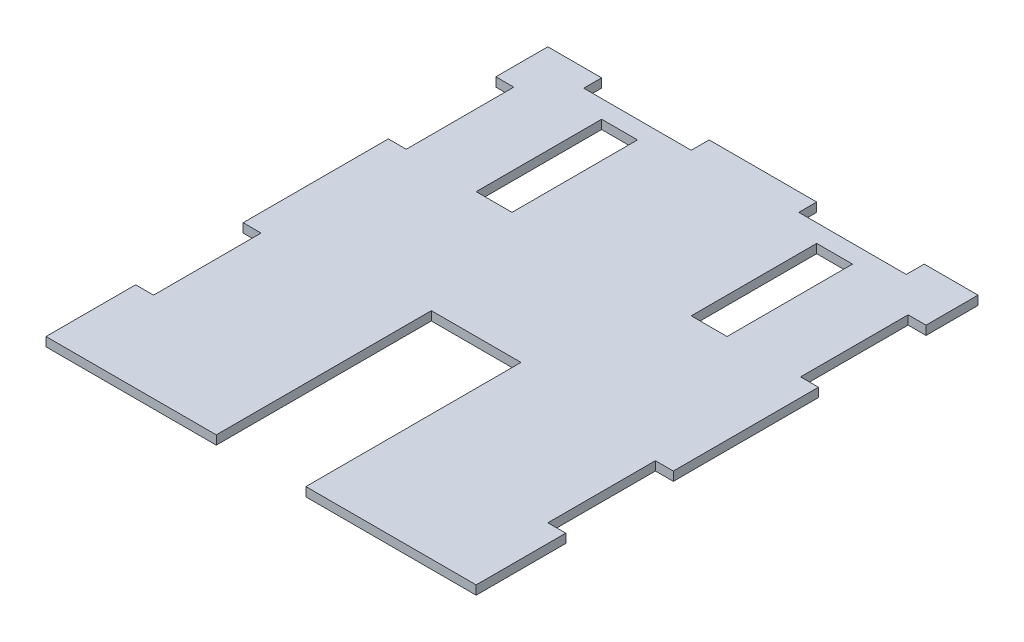
SolidWorks part; units mm, degrees
ref_plane "Front Plane" through (0, 0, 0) normal (0, 0, 1) x (1, 0, 0)
ref_plane "Top Plane" through (0, 0, 0) normal (0, 1, 0) x (1, 0, 0)
ref_plane "Right Plane" through (0, 0, 0) normal (1, 0, 0) x (0, 0, -1)
sketch "Sketch1" plane through (0, 0, 0) normal (0, 1, 0) x (1, 0, 0)
  line L1 (-152.4, -177.8) -> (152.4, -177.8)
  line L2 (-152.4, -177.8) -> (-152.4, 177.8)
  line L3 (-152.4, 177.8) -> (152.4, 177.8)
  line L4 (152.4, -177.8) -> (152.4, 177.8)
  line L5 (-152.4, -177.8) -> (152.4, 177.8) construction
  line L6 (-152.4, 177.8) -> (152.4, -177.8) construction
  point P0 (0, 0)
  dimension "D1" = 355.6
  dimension "D2" = 304.8
extrude "Boss-Extrude1" add sketch "Sketch1" along normal blind 6.35
sketch "Sketch2" plane through (0, 6.35, 0) normal (0, 1, 0) x (1, 0, 0)
  line L0 (-152.4, -177.8) -> (152.4, -177.8) construction
  line L1 (-31.75, -25.4) -> (31.75, -25.4)
  line L2 (-31.75, -25.4) -> (-31.75, -177.8)
  line L3 (-31.75, -177.8) -> (31.75, -177.8)
  line L4 (31.75, -25.4) -> (31.75, -177.8)
  line L5 (-31.75, -25.4) -> (31.75, -177.8) construction
  line L6 (-31.75, -177.8) -> (31.75, -25.4) construction
  point P0 (0, -101.6)
  dimension "D1" = 152.4
  dimension "D2" = 63.5
extrude "Cut-Extrude1" cut sketch "Sketch2" against normal through all
sketch "Sketch3" plane through (0, 6.35, 0) normal (0, 1, 0) x (1, 0, 0)
  line L0 (152.4, -177.8) -> (152.4, 177.8) construction
  line L1 (88.9, 152.4) -> (63.5, 152.4)
  line L2 (88.9, 152.4) -> (88.9, 63.5)
  line L3 (88.9, 63.5) -> (63.5, 63.5)
  line L4 (63.5, 152.4) -> (63.5, 63.5)
  line L5 (152.4, 177.8) -> (-152.4, 177.8) construction
  line L6 (0, -3.4925) -> (0, 3.4925) construction
  line L7 (-88.9, 63.5) -> (-63.5, 63.5)
  line L8 (-63.5, 152.4) -> (-63.5, 63.5)
  line L9 (-88.9, 152.4) -> (-63.5, 152.4)
  line L10 (-88.9, 152.4) -> (-88.9, 63.5)
  dimension "D1" = 63.5
  dimension "D2" = 88.9
  dimension "D3" = 25.4
  dimension "D4" = 114.3
extrude "Cut-Extrude2" cut sketch "Sketch3" against normal through all
sketch "Sketch4" plane through (0, 6.35, 0) normal (0, 1, 0) x (1, 0, 0)
  line L0 (-152.4, 177.8) -> (-152.4, -177.8) construction
  line L1 (-152.4, 140.97) -> (-139.7, 140.97)
  line L2 (-152.4, 140.97) -> (-152.4, 64.77)
  line L3 (-152.4, 64.77) -> (-139.7, 64.77)
  line L4 (-139.7, 140.97) -> (-139.7, 64.77)
  line L5 (0, -3.4925) -> (0, 3.4925) construction
  line L6 (-152.4, -114.3) -> (-139.7, -114.3)
  line L7 (-152.4, -114.3) -> (-152.4, -38.1)
  line L8 (-152.4, -38.1) -> (-139.7, -38.1)
  line L9 (-139.7, -114.3) -> (-139.7, -38.1)
  line L10 (152.4, 64.77) -> (139.7, 64.77)
  line L11 (139.7, 140.97) -> (139.7, 64.77)
  line L12 (152.4, 140.97) -> (139.7, 140.97)
  line L13 (152.4, 140.97) -> (152.4, 64.77)
  line L14 (152.4, -38.1) -> (139.7, -38.1)
  line L15 (139.7, -114.3) -> (139.7, -38.1)
  line L16 (152.4, -114.3) -> (139.7, -114.3)
  line L17 (152.4, -114.3) -> (152.4, -38.1)
  line L18 (152.4, 177.8) -> (-152.4, 177.8) construction
  line L19 (114.3, 165.1) -> (38.1, 165.1)
  line L20 (-114.3, 177.8) -> (-38.1, 177.8)
  line L21 (-114.3, 177.8) -> (-114.3, 165.1)
  line L22 (-114.3, 165.1) -> (-38.1, 165.1)
  line L23 (-38.1, 177.8) -> (-38.1, 165.1)
  line L24 (38.1, 177.8) -> (38.1, 165.1)
  line L25 (114.3, 177.8) -> (38.1, 177.8)
  line L26 (114.3, 177.8) -> (114.3, 165.1)
  dimension "D1" = 12.7
  dimension "D2" = 12.7
  dimension "D3" = 76.2
  dimension "D4" = 76.2
  dimension "D5" = 36.83
  dimension "D6" = 215.9
  dimension "D7" = 12.7
  dimension "D8" = 76.2
  dimension "D9" = 76.2
extrude "Cut-Extrude3" cut sketch "Sketch4" against normal through all
